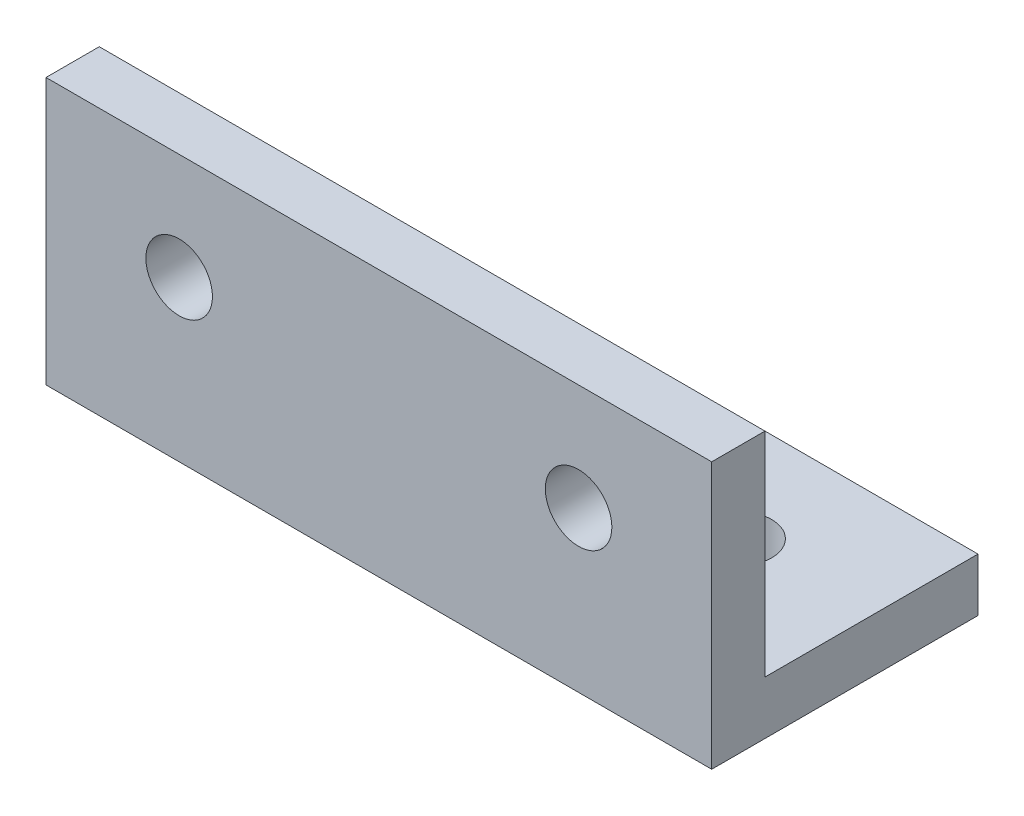
SolidWorks part; units mm, degrees
ref_plane "Спереди" through (0, 0, 0) normal (0, 0, 1) x (1, 0, 0)
ref_plane "Сверху" through (0, 0, 0) normal (0, 1, 0) x (1, 0, 0)
ref_plane "Справа" through (0, 0, 0) normal (1, 0, 0) x (0, 0, -1)
sketch "Эскиз1" plane through (0, 0, 0) normal (0, 1, 0) x (1, 0, 0)
  line L0 (0, 12) -> (50, 12) construction
  line L1 (0, 0) -> (50, 0)
  line L2 (0, 0) -> (0, 20)
  line L3 (0, 20) -> (50, 20)
  line L4 (50, 0) -> (50, 20)
  circle A0 centre (10, 12) radius 2.5
  circle A1 centre (40, 12) radius 2.5
  dimension "D4" = 5
  dimension "D5" = 5
  dimension "D1" = 50
  dimension "D2" = 20
  dimension "D3" = 12
  dimension "D6" = 10
  dimension "D7" = 30
extrude "Бобышка-Вытянуть1" add sketch "Эскиз1" along normal blind 4
sketch "Эскиз2" plane through (0, 4, 0) normal (0, 1, 0) x (1, 0, 0)
  line L0 (50, 0) -> (50, 20) construction
  line L1 (0, 0) -> (50, 0)
  line L2 (0, 0) -> (0, 4)
  line L3 (0, 4) -> (50, 4)
  line L4 (50, 0) -> (50, 4)
  dimension "D1" = 4
extrude "Бобышка-Вытянуть2" add sketch "Эскиз2" along normal blind 16
sketch "Эскиз3" plane through (0, 0, 0) normal (0, 0, 1) x (1, 0, 0)
  line L0 (0, 12) -> (50, 12) construction
  line L1 (0, 20) -> (0, 0) construction
  line L2 (50, 20) -> (50, 0) construction
  line L3 (0, 0) -> (50, 0) construction
  circle A0 centre (10, 12) radius 2.5
  circle A1 centre (40, 12) radius 2.5
  dimension "D2" = 5
  dimension "D3" = 5
  dimension "D1" = 12
  dimension "D4" = 10
  dimension "D5" = 30
extrude "Вырез-Вытянуть1" cut sketch "Эскиз3" against normal blind 4
